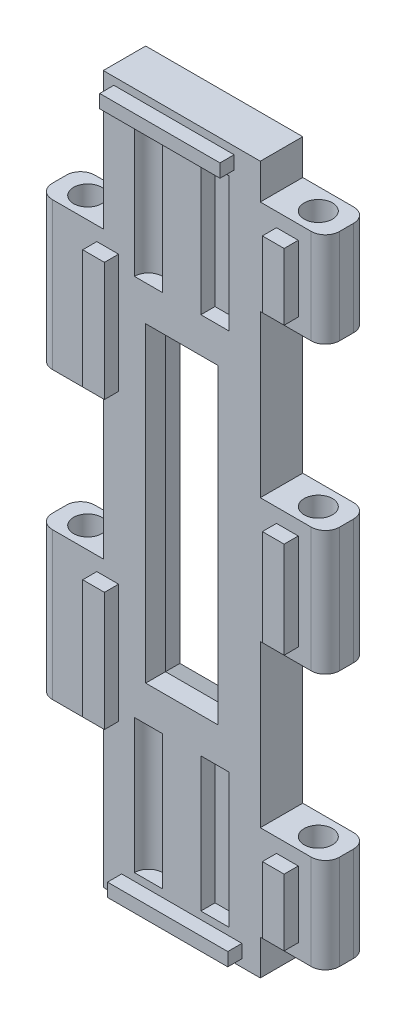
SolidWorks part; units mm, degrees
ref_plane "Ebene vorne" through (0, 0, 0) normal (0, 0, 1) x (1, 0, 0)
ref_plane "Ebene oben" through (0, 0, 0) normal (0, 1, 0) x (1, 0, 0)
ref_plane "Ebene rechts" through (0, 0, 0) normal (1, 0, 0) x (0, 0, -1)
sketch "Skizze1" plane through (0, 0, 0) normal (0, 0, 1) x (1, 0, 0)
  line L0 (-15.7, 49.2206) -> (-15.7, -0.7794)
  line L1 (-15.7, -0.7794) -> (-4.6, -0.7794)
  line L2 (-4.6, -0.7794) -> (-4.6, 49.2206)
  line L3 (-4.6, 49.2206) -> (-15.7, 49.2206)
  line L4 (-15.7, 39.5206) -> (-20.3, 39.5206)
  line L5 (-20.3, 39.5206) -> (-20.3, 29.1206)
  line L6 (-20.3, 29.1206) -> (-15.7, 29.1206)
  line L7 (-15.7, 8.9206) -> (-20.3, 8.9206)
  line L8 (-20.3, 8.9206) -> (-20.3, 19.3206)
  line L9 (-20.3, 19.3206) -> (-15.7, 19.3206)
  line L10 (-4.6, 8.4206) -> (0, 8.4206)
  line L11 (0, 8.4206) -> (0, 1.7206)
  line L12 (0, 1.7206) -> (-4.6, 1.7206)
  line L13 (-4.6, 40.0206) -> (0, 40.0206)
  line L14 (0, 40.0206) -> (0, 46.7206)
  line L15 (0, 46.7206) -> (-4.6, 46.7206)
  line L16 (-4.6, 28.6206) -> (0, 28.6206)
  line L17 (0, 28.6206) -> (0, 19.8206)
  line L18 (0, 19.8206) -> (-4.6, 19.8206)
  dimension "D2" = 11.1
  dimension "D3" = 0.5
  dimension "D4" = 6.7
  dimension "D5" = 0.5
  dimension "D6" = 50
  dimension "D7" = 0.5
  dimension "D8" = 4.6
  dimension "D9" = 11.4
  dimension "1" = 6.7
  dimension "D10" = 4.6
  dimension "D11" = 2.5
  dimension "D12" = 8.8
  dimension "D13" = 2.5
  dimension "D14" = 0.5
  dimension "D15" = 4.6
  dimension "D16" = 4.6
extrude "Aufsatz-Linear austragen1" add sketch "Skizze1" along normal blind 3 contours L9 L8 L7 L0 | L2 L3 L0 L1 | L5 L6 L0 L4 | L14 L15 L2 L13 | L12 L11 L10 L2 | L17 L2 region at (-10.15, 24.2206, 0) region at (-18, 34.3206, 0) region at (-2.3, 43.3706, 0) region at (-18, 14.1206, 0) region at (-2.3, 24.2206, 0) region at (-2.3, 5.0706, 0)
sketch "Skizze2" plane through (0, 39.5206, 0) normal (0, 1, 0) x (1, 0, 0)
  line L1 (-20.3, -1.5) -> (0, -1.5) construction
  line L2 (-10.15, 0) -> (-10.15, -3) construction
  line L3 (-20.3, -3) -> (-20.3, 0) construction
  line L5 (0, -3) -> (0, 0) construction
  line L6 (-4.6, 0) -> (-15.7, 0) construction
  line L7 (-4.6, -3) -> (-15.7, -3) construction
  circle A0 centre (-18.3, -1.5) radius 1
  circle A1 centre (-2, -1.5) radius 1
  dimension "D1" = 2
  dimension "D2" = 8.15
  dimension "D6" = 2
  dimension "D3" = 8.15
extrude "Schnitt-Linear austragen1" cut sketch "Skizze2" along normal blind 37.5 and the other way blind 67.5
sketch "Skizze3" plane through (0, 0, 3) normal (0, 0, 1) x (1, 0, 0)
  line L0 (-12.7, 13.2206) -> (-12.7, 35.2206)
  line L1 (-12.7, 35.2206) -> (-7.6, 35.2206)
  line L2 (-7.6, 35.2206) -> (-7.6, 13.2206)
  line L3 (-7.6, 13.2206) -> (-12.7, 13.2206)
  line L4 (-15.7, -0.7794) -> (-4.6, -0.7794) construction
  line L5 (-15.7, 29.1206) -> (-15.7, 19.3206) construction
  line L6 (-4.6, 8.4206) -> (-4.6, 19.8206) construction
  point P6 (-10.15, -0.7794)
  dimension "D1" = 22
  dimension "D2" = 14
  dimension "D3" = 3
  dimension "D4" = 3
extrude "Schnitt-Linear austragen2" cut sketch "Skizze3" against normal blind 7.5
fillet "Verrundung4" radius 1 10 edges at (0, 43.3706, 0) (0, 43.3706, 3) (0, 24.2206, 0) (0, 24.2206, 3) (0, 5.0706, 0) (0, 5.0706, 3) (-20.3, 14.1206, 0) (-20.3, 14.1206, 3) (-20.3, 34.3206, 0) (-20.3, 34.3206, 3)
sketch "Skizze4" plane through (0, 0, 3) normal (0, 0, 1) x (1, 0, 0)
  line L0 (-13.5, 47.2206) -> (-13.5, 37.7206)
  line L1 (-13.5, 37.7206) -> (-11.5, 37.7206)
  line L2 (-11.5, 37.7206) -> (-11.5, 47.2206)
  line L3 (-11.5, 47.2206) -> (-13.5, 47.2206)
  line L4 (-13.5, 10.7206) -> (-13.5, 1.2206)
  line L5 (-13.5, 1.2206) -> (-11.5, 1.2206)
  line L6 (-11.5, 1.2206) -> (-11.5, 10.7206)
  line L7 (-11.5, 10.7206) -> (-13.5, 10.7206)
  line L9 (-15.7, 8.9206) -> (-15.7, -0.7794) construction
  line L10 (-12.7, 13.2206) -> (-7.6, 13.2206) construction
  line L13 (-7.6, 35.2206) -> (-12.7, 35.2206) construction
  line L14 (-8.8, 47.2206) -> (-8.8, 37.7206)
  line L15 (-8.8, 37.7206) -> (-6.8, 37.7206)
  line L16 (-6.8, 37.7206) -> (-6.8, 47.2206)
  line L17 (-6.8, 47.2206) -> (-8.8, 47.2206)
  line L18 (-8.8, 10.7206) -> (-8.8, 1.2206)
  line L19 (-8.8, 1.2206) -> (-6.8, 1.2206)
  line L20 (-6.8, 1.2206) -> (-6.8, 10.7206)
  line L21 (-6.8, 10.7206) -> (-8.8, 10.7206)
  line L22 (-4.6, 8.4206) -> (-4.6, 19.8206) construction
  dimension "D1" = 9.5
  dimension "D2" = 2.5
  dimension "D3" = 2.2
  dimension "D4" = 2.5
  dimension "D5" = 9.5
  dimension "D6" = 2.2
  dimension "D7" = 2
  dimension "D8" = 2
  dimension "D9" = 2
  dimension "D10" = 2
  dimension "D11" = 2.5
  dimension "D12" = 2.5
  dimension "D13" = 9.5
  dimension "D14" = 9.5
extrude "Schnitt-Linear austragen3" cut sketch "Skizze4" against normal blind 1
fillet "Verrundung5" radius 1 4 edges at (-6.8, 5.9706, 2) (-13.5, 5.9706, 2) (-13.5, 42.4706, 2) (-6.8, 42.4706, 2)
sketch "Skizze7" plane through (0, 0, 3) normal (0, 0, 1) x (1, 0, 0)
  line L0 (-14.95, 48.6906) -> (-6.45, 48.6906)
  line L1 (-6.45, 48.6906) -> (-6.45, 47.7506)
  line L2 (-6.45, 47.7506) -> (-14.95, 47.7506)
  line L3 (-14.95, 47.7506) -> (-14.95, 48.6906)
  line L4 (-4.6, 49.2206) -> (-15.7, 49.2206) construction
  line L5 (-6.8, 47.2206) -> (-8.8, 47.2206) construction
  line L6 (-10.15, -0.7794) -> (-10.15, 0.6906) construction
  line L8 (-15.7, 49.2206) -> (-15.7, 39.5206) construction
  line L18 (-14.4, 0.6906) -> (-5.9, 0.6906)
  line L19 (-5.9, 0.6906) -> (-5.9, -0.2494)
  line L20 (-5.9, -0.2494) -> (-14.4, -0.2494)
  line L21 (-14.4, -0.2494) -> (-14.4, 0.6906)
  line L22 (-8.8, 1.2206) -> (-6.8, 1.2206) construction
  line L23 (-15.7, -0.7794) -> (-4.6, -0.7794) construction
  line L24 (-16.1544, 18.3206) -> (-16.1544, 9.9206)
  line L25 (-16.1544, 9.9206) -> (-14.6161, 9.9206)
  line L26 (-14.6161, 9.9206) -> (-14.6161, 18.3206)
  line L27 (-14.6161, 18.3206) -> (-16.1544, 18.3206)
  line L28 (-3.4546, 7.4206) -> (-3.4546, 2.7206)
  line L29 (-3.4546, 2.7206) -> (-1.9163, 2.7206)
  line L30 (-1.9163, 2.7206) -> (-1.9163, 7.4206)
  line L31 (-1.9163, 7.4206) -> (-3.4546, 7.4206)
  line L32 (-3.4546, 27.6206) -> (-3.4546, 20.8206)
  line L33 (-3.4546, 20.8206) -> (-1.9163, 20.8206)
  line L34 (-1.9163, 20.8206) -> (-1.9163, 27.6206)
  line L35 (-1.9163, 27.6206) -> (-3.4546, 27.6206)
  line L36 (-16.1544, 38.5206) -> (-16.1544, 30.1206)
  line L37 (-16.1544, 30.1206) -> (-14.6161, 30.1206)
  line L38 (-14.6161, 30.1206) -> (-14.6161, 38.5206)
  line L39 (-14.6161, 38.5206) -> (-16.1544, 38.5206)
  line L40 (-3.4546, 45.7206) -> (-3.4546, 41.0206)
  line L41 (-3.4546, 41.0206) -> (-1.9163, 41.0206)
  line L42 (-1.9163, 41.0206) -> (-1.9163, 45.7206)
  line L43 (-1.9163, 45.7206) -> (-3.4546, 45.7206)
  line L46 (-4.6, 40.0206) -> (-1, 40.0206) construction
  line L47 (-1, 46.7206) -> (-4.6, 46.7206) construction
  line L48 (-4.6, 28.6206) -> (-1, 28.6206) construction
  line L50 (-15.7, 39.5206) -> (-19.3, 39.5206) construction
  line L51 (-15.7, 8.9206) -> (-19.3, 8.9206) construction
  line L52 (-19.3, 19.3206) -> (-15.7, 19.3206) construction
  line L53 (-4.6, 8.4206) -> (-1, 8.4206) construction
  line L54 (-1, 1.7206) -> (-4.6, 1.7206) construction
  dimension "D1" = 0.53
  dimension "D2" = 0.53
  dimension "D3" = 8.5
  dimension "D4" = 0.75
  dimension "D5" = 0.53
  dimension "D6" = 0.53
  dimension "D7" = 1
  dimension "D8" = 1
  dimension "D9" = 1
  dimension "D10" = 1
  dimension "D11" = 1
  dimension "D12" = 1
  dimension "D13" = 1
  dimension "D14" = 1
  dimension "D15" = 1
  dimension "D16" = 1
  dimension "D17" = 8.5
extrude "Aufsatz-Linear austragen4" add sketch "Skizze7" along normal blind 1
chamfer "Fase1" distance 1.6 angle 20 4 edges at (-10.15, 13.2206, 0) (-12.7, 24.2206, 0) (-10.15, 35.2206, 0) (-7.6, 24.2206, 0) first distance on face at (-10.15, 13.2206, 1.5) first distance on face at (-12.7, 24.2206, 1.5) first distance on face at (-10.15, 35.2206, 1.5) first distance on face at (-7.6, 24.2206, 1.5)
